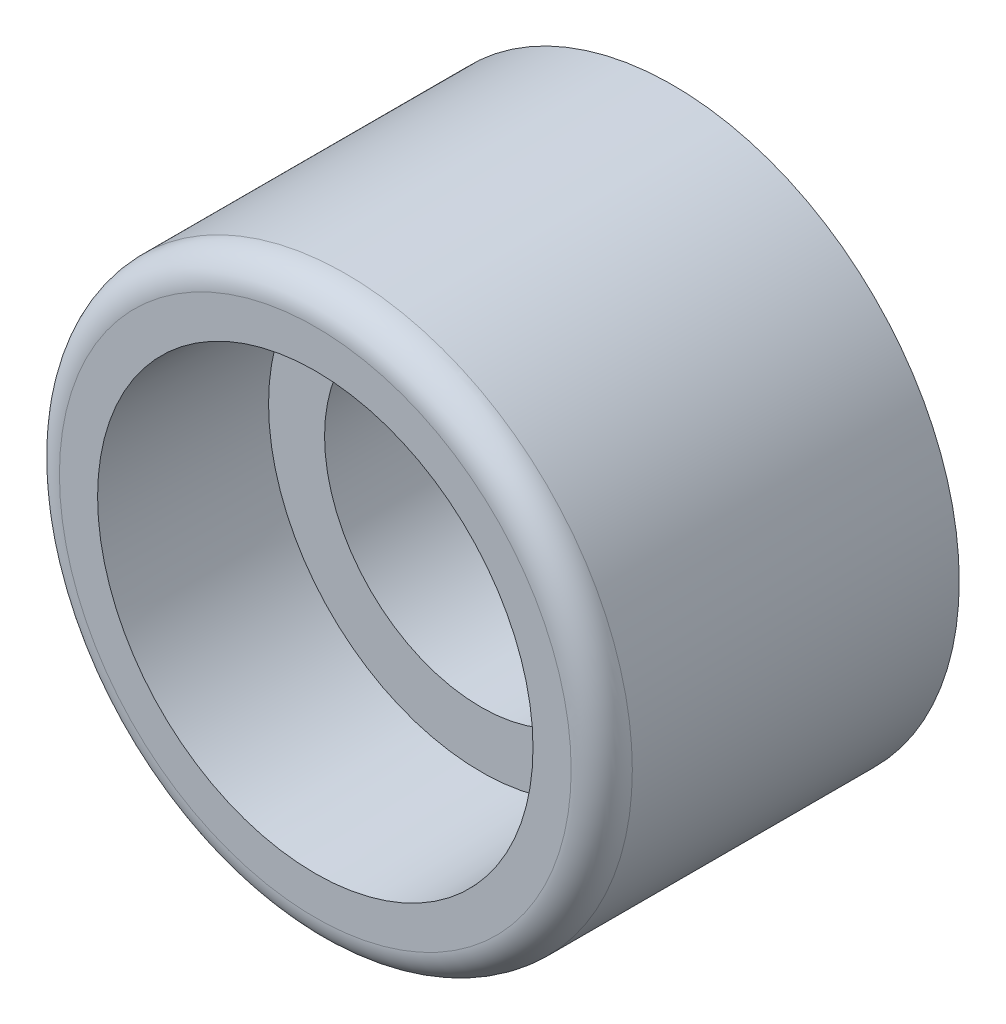
SolidWorks part; units mm, degrees
extrude "Body" add sketch "BodySch" along normal mid plane 39.624
sketch "BodySch" plane through (0, 0, 0) normal (0, 0, 1) x (1, 0, 0)
  circle A0 centre (0, 0) radius 31.75
  dimension "Dia" = 63.5
material "PW90:Mi:0:191:Ar:0:-1:C1:1:2:3:Re:17:Ts:18:19:20:21:22:23:"
ref_plane "Front" through (0, 0, 0) normal (0, 0, 1) x (1, 0, 0)
ref_plane "Top" through (0, 0, 0) normal (0, 1, 0) x (1, 0, 0)
ref_plane "Right" through (0, 0, 0) normal (1, 0, 0) x (0, 0, -1)
sketch "FlowSch" plane through (0, 0, -19.812) normal (0, 0, 1) x (1, 0, 0)
  circle A0 centre (0, 0) radius 17.3507
  dimension "Dia" = 34.7015
extrude "Flow" cut sketch "FlowSch" along normal up to surface (39.624 mm away) up to face at (31.75, 0, 19.812)
sketch "ThreadSch" plane through (0, 0, 0) normal (1, 0, 0) x (0, 0, -1)
  line L0 (0, 0) -> (-19.812, 0) construction
  line L1 (-19.812, 0) -> (19.812, 0) construction
  line L2 (-1.4351, 0) -> (-1.4351, 23.5578)
  line L3 (-1.4351, 23.5578) -> (-19.812, 24.13)
  line L4 (-19.812, 24.13) -> (-19.812, 0)
  line L5 (-19.812, 0) -> (-1.4351, 0)
  line L6 (-19.812, 31.75) -> (-19.812, -31.75) construction
  dimension "D1" = 1.783
revolve "Thread" cut sketch "ThreadSch" angle 360 about L0
fillet "Fillet1" radius 3.3896 1 edges at (31.75, 0, 19.812)
sketch "CPointSketch" plane through (0, 0, 1.4351) normal (0, 0, 1) x (1, 0, 0)
  circle A0 centre (0, 0) radius 23.5578 construction
  circle A1 centre (0, 0) radius 23.5578
other "CPoint1" parameters "Diameter"=38.1, "StubLength"=0
ref_axis "Axis1" through (0, 0, 11.4351) along (0, 0, -1)
equation "\"EdgeRadius@Fillet1\" =  ( \"Dia@ThreadSch\" - \"Dia@FlowSch\" )  / 4"
